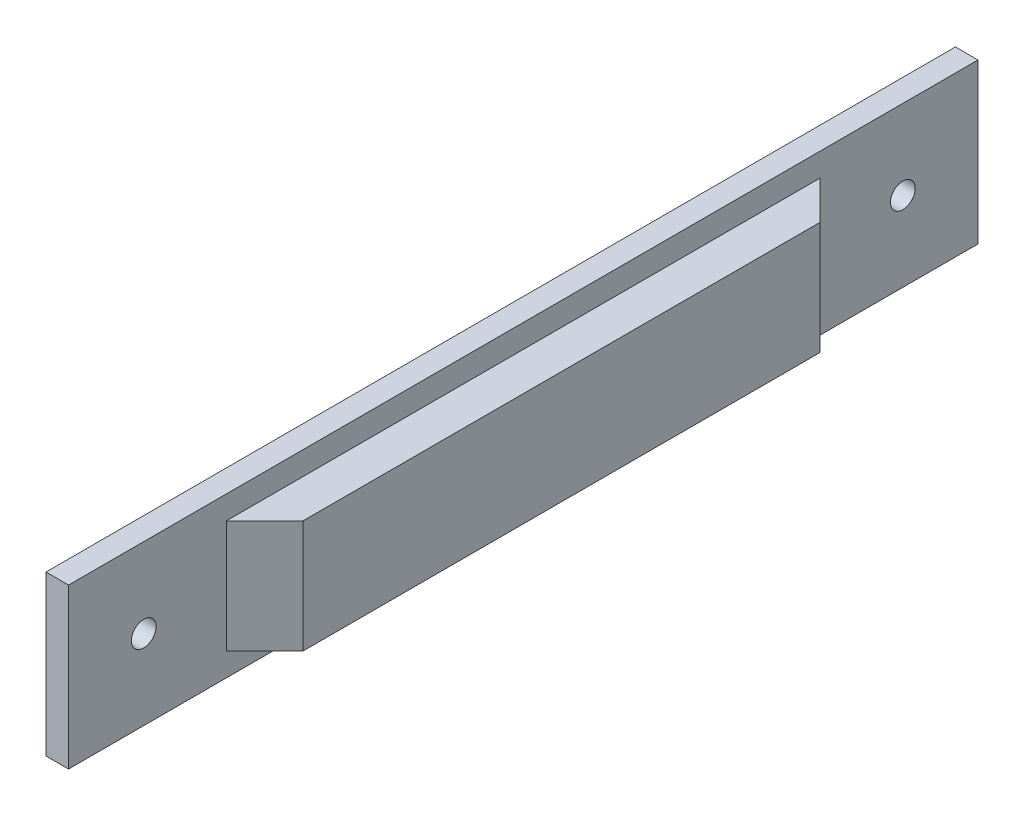
SolidWorks part; units mm, degrees
ref_plane "前视基准面" through (0, 0, 0) normal (0, 0, 1) x (1, 0, 0)
ref_plane "上视基准面" through (0, 0, 0) normal (0, 1, 0) x (1, 0, 0)
ref_plane "右视基准面" through (0, 0, 0) normal (1, 0, 0) x (0, 0, -1)
sketch "草图1" plane through (0, 0, 0) normal (0, 0, 1) x (1, 0, 0)
  line L1 (0, 0) -> (15.2, 0)
  line L2 (0, 0) -> (0, 15.2)
  line L3 (0, 15.2) -> (15.2, 15.2)
  line L4 (15.2, 0) -> (15.2, 15.2)
  dimension "D1" = 15.2
  dimension "D2" = 15.2
extrude "拉伸-薄壁1" add sketch "草图1" along normal blind 121 thin thin type one direction wall 3
sketch "草图2" plane through (-3, 0, 0) normal (-1, 0, 0) x (0, 0, 1)
  line L0 (0, 18.2) -> (0, -3) construction
  line L1 (121, 18.2) -> (121, -3) construction
  line L2 (121, -3) -> (0, -3) construction
  circle A0 centre (10, 7.6) radius 1.65
  circle A1 centre (111, 7.6) radius 1.65
  dimension "D1" = 3.3
  dimension "D2" = 3.3
  dimension "D3" = 10
  dimension "D4" = 10
  dimension "D5" = 10.6
extrude "切除-拉伸1" cut sketch "草图2" against normal blind 30
sketch "草图3" plane through (18.2, 0, 0) normal (1, 0, 0) x (0, 0, -1)
  line L1 (-121, 18.2) -> (0, 18.2)
  line L2 (-121, 18.2) -> (-121, -3)
  line L3 (-121, -3) -> (0, -3)
  line L4 (0, 18.2) -> (0, -3)
extrude "切除-拉伸2" cut sketch "草图3" against normal blind 18.2
sketch "草图4" plane through (0, 0, 0) normal (1, 0, 0) x (0, 0, -1)
  line L0 (0, 18.2) -> (0, -3) construction
  line L1 (-94.9, 15.1) -> (-26.1, 15.1)
  line L2 (-94.9, 15.1) -> (-94.9, 0.1)
  line L3 (-94.9, 0.1) -> (-26.1, 0.1)
  line L4 (-26.1, 15.1) -> (-26.1, 0.1)
  line L5 (-121, 18.2) -> (-121, -3) construction
  line L6 (-121, -3) -> (0, -3) construction
  line L7 (0, 18.2) -> (-121, 18.2) construction
  point P8 (-26.1, 7.6)
  dimension "D1" = 26.1
  dimension "D2" = 26.1
  dimension "D3" = 15
  dimension "D4" = 10.6
  dimension "D5" = 3.1
  dimension "D6" = 3.1
extrude "凸台-拉伸1" add sketch "草图4" along normal blind 5.1
chamfer "倒角1" distance 5.1 angle 45 2 edges at (0, 7.6, 26.1) (0, 7.6, 94.9)
